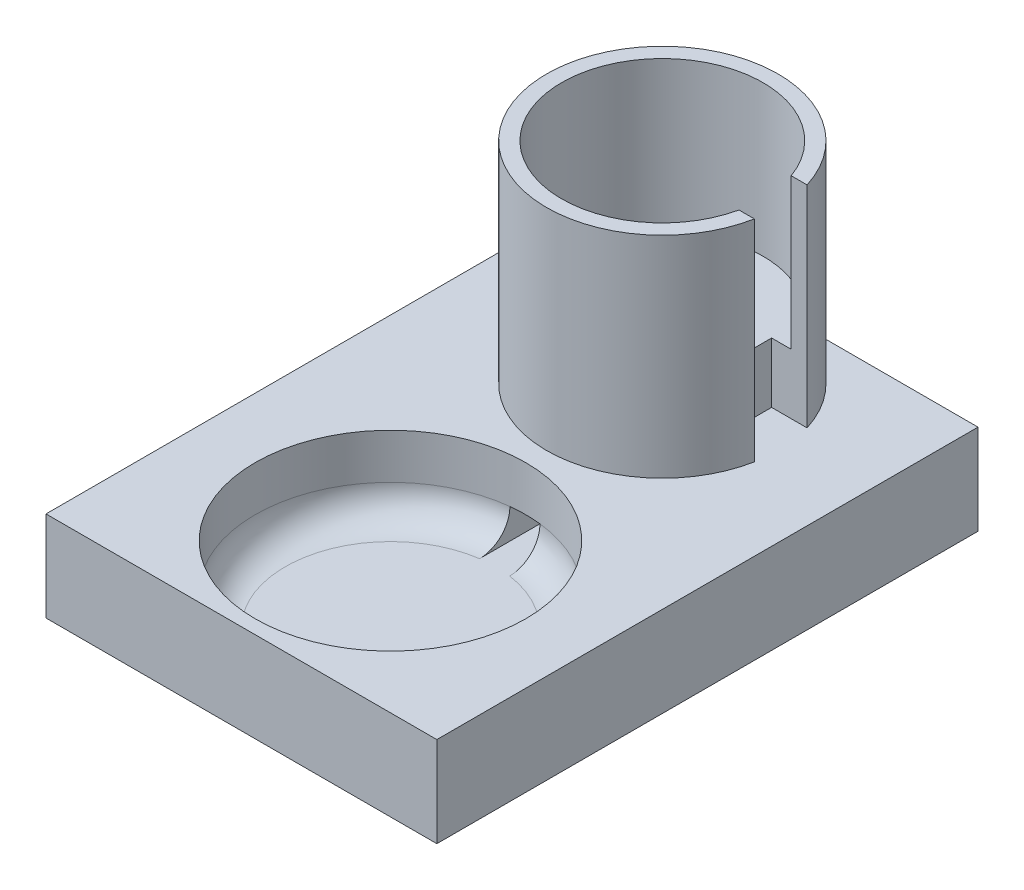
SolidWorks part; units mm, degrees
ref_plane "前视基准面" through (0, 0, 0) normal (0, 0, 1) x (1, 0, 0)
ref_plane "上视基准面" through (0, 0, 0) normal (0, 1, 0) x (1, 0, 0)
ref_plane "右视基准面" through (0, 0, 0) normal (1, 0, 0) x (0, 0, -1)
sketch "草图1" plane through (0, 0, 0) normal (0, 0, 1) x (1, 0, 0)
  line L1 (-65, 30) -> (65, 30)
  line L2 (-65, 30) -> (-65, 0)
  line L3 (-65, 0) -> (65, 0)
  line L4 (65, 30) -> (65, 0)
  dimension "D1" = 130
  dimension "D2" = 65
  dimension "D3" = 30
extrude "凸台-拉伸1" add sketch "草图1" against normal blind 180
sketch "草图2" plane through (0, 30, 0) normal (0, 1, 0) x (1, 0, 0)
  circle A0 centre (0, 140) radius 33.5
  point P2 (0, 145)
  point P4 (0, 0)
  point P5 (0, 48.0129)
  point P6 (0, 53.4282)
  point P7 (0, 0)
  dimension "D1" = 67
  dimension "D2" = 140
extrude "拉伸-薄壁1" add sketch "草图2" along normal blind 70 thin contours A0 thin type one direction wall 5
sketch "草图3" plane through (0, 30, 0) normal (0, 1, 0) x (1, 0, 0)
  circle A0 centre (0, 49.5718) radius 45
  point P2 (0, 0)
  point P3 (0, 54.6745)
  point P4 (0, 49.5718)
  dimension "D1" = 90
extrude "切除-拉伸1" cut sketch "草图3" against normal blind 25
ref_plane "基准面1" through (0, 50, 0) normal (0, 1, 0) x (1, 0, 0)
sketch "草图4" plane through (0, 50, 0) normal (0, 1, 0) x (1, 0, 0)
  circle A0 centre (0, 140) radius 20
  dimension "D1" = 40
  dimension "D2" = 140
sketch "草图5" plane through (0, 30, 0) normal (0, 1, 0) x (1, 0, 0)
  circle A0 centre (0, 140) radius 33.5
extrude "凸台-拉伸2" add sketch "草图5" along normal blind 20
extrude "切除-拉伸2" cut sketch "草图4" against normal blind 40
ref_plane "基准面2" through (0, 0, -20) normal (0, 0, 1) x (1, 0, 0)
sketch "草图7" plane through (0, 0, -20) normal (0, 0, 1) x (1, 0, 0)
  line L0 (-65, 0) -> (65, 0) construction
  line L1 (-5, 15) -> (5, 15)
  line L2 (-5, 15) -> (-5, 5)
  line L3 (-5, 5) -> (5, 5)
  line L4 (5, 15) -> (5, 5)
  dimension "D1" = 10
  dimension "D2" = 5
  dimension "D3" = 5
  dimension "D4" = 10
extrude "切除-拉伸3" cut sketch "草图7" against normal blind 130
sketch "草图8" plane through (65, 0, 0) normal (1, 0, 0) x (0, 0, -1)
  line L0 (180, 30) -> (0, 30) construction
  line L1 (132.7929, 106.5552) -> (151.3519, 106.5552)
  line L2 (132.7929, 106.5552) -> (132.7929, 30)
  line L3 (132.7929, 30) -> (151.3519, 30)
  line L4 (151.3519, 106.5552) -> (151.3519, 30)
extrude "切除-拉伸4" cut sketch "草图8" against normal blind 40
fillet "圆角1" radius 10 1 edges at (0, 5, -4.5718)
